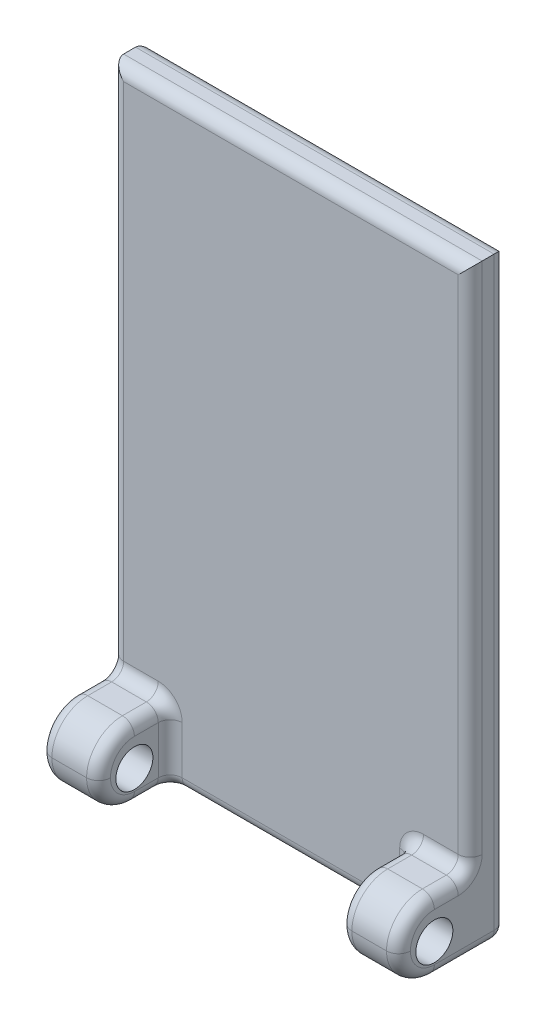
SolidWorks part; units mm, degrees
ref_plane "Front Plane" through (0, 0, 0) normal (0, 0, 1) x (1, 0, 0)
ref_plane "Top Plane" through (0, 0, 0) normal (0, 1, 0) x (1, 0, 0)
ref_plane "Right Plane" through (0, 0, 0) normal (1, 0, 0) x (0, 0, -1)
sketch "Sketch1" plane through (0, 0, 0) normal (0, 0, 1) x (1, 0, 0)
  line L1 (-15, -25) -> (15, -25)
  line L2 (-15, -25) -> (-15, 25)
  line L3 (-15, 25) -> (15, 25)
  line L4 (15, -25) -> (15, 25)
  line L5 (-15, -25) -> (15, 25) construction
  line L6 (-15, 25) -> (15, -25) construction
  point P0 (0, 0)
  dimension "D1" = 50
  dimension "D2" = 30
extrude "Boss-Extrude1" add sketch "Sketch1" along normal blind 3
sketch "Sketch2" plane through (0, 0, 3) normal (0, 0, 1) x (1, 0, 0)
  line L0 (0, -25) -> (0, 25) construction
  line L1 (15, 25) -> (-15, 25) construction
  line L3 (-15, -25) -> (-10.1, -25)
  line L4 (-15, -25) -> (-15, -19)
  line L5 (-15, -19) -> (-10.1, -19)
  line L6 (-10.1, -25) -> (-10.1, -19)
  point P6 (0, 0)
  dimension "D1" = 4.9
  dimension "D2" = 6
extrude "Boss-Extrude2" add sketch "Sketch2" along normal blind 6
sketch "Sketch3" plane through (-15, 0, 0) normal (-1, 0, 0) x (0, 0, 1)
  line L0 (9, -25) -> (0, -25) construction
  line L2 (3, 25) -> (3, -19) construction
  circle A0 centre (6, -22.3) radius 1.55
  point P4 (0, 0)
  dimension "D1" = 3.1
  dimension "D2" = 2.7
  dimension "D3" = 3
extrude "Cut-Extrude1" cut sketch "Sketch3" against normal through all
mirror "Mirror1" about plane through (0, 0, 0) normal (1, 0, 0) of "Cut-Extrude1", "Boss-Extrude2"
fillet "Fillet1" radius 3 4 edges at (12.55, -25, 9) (12.55, -19, 9) (-12.55, -19, 9) (-12.55, -25, 9)
fillet "Fillet2" radius 1 28 edges at (-10.1, -19, 4.5) (10.1, -19, 4.5) (-15, -25, 3) (-10.1, -19.8787, 8.1213) (10.1, -19.8787, 8.1213) (-15, -24.1213, 8.1213) (-10.1, -24.1213, 8.1213) (10.1, -24.1213, 8.1213) (-15, -19.8787, 8.1213) (-10.1, -25, 4.5) (10.1, -25, 4.5) (-15, -19, 4.5) (15, -19, 4.5) (15, -19.8787, 8.1213) (15, -25, 3) (0, 25, 0) (-15, 0, 0) (0, -25, 0) (15, 0, 0) (0, -25, 3) (-10.1, -22, 3) (-12.55, -19, 3) (-15, 3, 3) (0, 25, 3) (15, 3, 3) (12.55, -19, 3) (10.1, -22, 3) (15, -24.1213, 8.1213)
